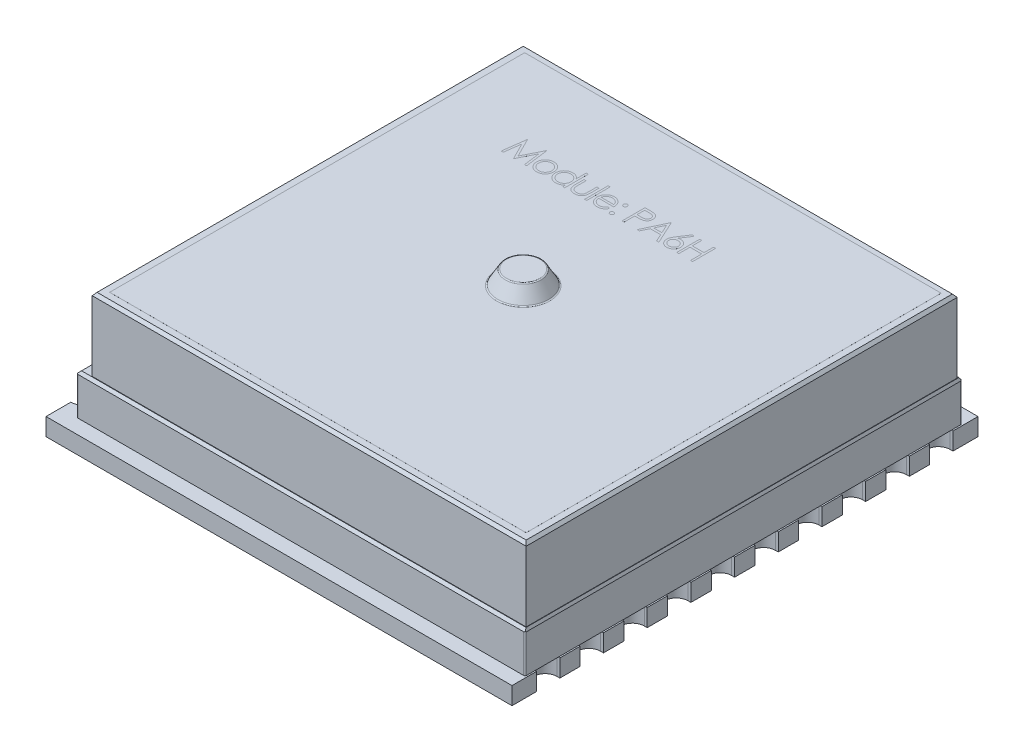
SolidWorks part; units mm, degrees
note: The reader was unsure of these and kept them because the rebuilt part matched: shared geometry of "Esboço11<8>", "Esboço11<9>", "Esboço11<11>", "Esboço11<12>", "Esboço11<15>", "Esboço11<16>", "Esboço11<17>", "Esboço11<19>", "Esboço11<20>".
ref_plane "Front Plane" through (0, 0, 0) normal (0, 0, 1) x (1, 0, 0)
ref_plane "Top Plane" through (0, 0, 0) normal (0, 1, 0) x (1, 0, 0)
ref_plane "Right Plane" through (0, 0, 0) normal (1, 0, 0) x (0, 0, -1)
sketch "Esboço1" plane through (0, 0, 0) normal (0, 1, 0) x (1, 0, 0)
  line L1 (0, 0) -> (16, 0)
  line L2 (0, 0) -> (0, -16)
  line L3 (0, -16) -> (16, -16)
  line L4 (16, 0) -> (16, -16)
  dimension "D1" = 16
  dimension "D2" = 16
extrude "BaseInicio" add sketch "Esboço1" along normal blind 0.6
sketch "Esboço2" plane through (0, 0.6, 0) normal (0, 1, 0) x (1, 0, 0)
  line L7 (0.55, -0.5) -> (15.95, -0.5)
  line L9 (15.95, -0.5) -> (15.95, -15.5)
  line L11 (15.95, -15.5) -> (0.55, -15.5)
  line L13 (0.55, -0.5) -> (0.55, -15.5)
extrude "BaseMeio" add sketch "Esboço2" along normal blind 1.4
sketch "Esboço5" plane through (0, 2, 0) normal (0, 1, 0) x (1, 0, 0)
  line L24 (1, -15.4145) -> (15.9, -15.4145)
  line L28 (1, -0.6145) -> (1, -15.4145)
  line L29 (1, -0.6145) -> (15.9, -0.6145)
  line L30 (15.9, -0.6145) -> (15.9, -15.4145)
extrude "BaseFim" add sketch "Esboço5" along normal blind 2.5
sketch "Esboço9" plane through (0, 4.5, 0) normal (0, 1, 0) x (1, 0, 0)
  circle A0 centre (8.2, -7.8145) radius 0.6
extrude "Chapeu" add sketch "Esboço9" along normal blind 0.5
draft "InclinaçãoChapeu" type of draft neutral plane draft angle 30 faces to draft 1 face at (8.2, 5, 8.4145) neutral plane through (8.2, 5, 7.8145) neutral plane normal (0, 1, 0) parameters "D1"=30
sketch "Esboço10" plane through (0, 0, 0) normal (0, -1, 0) x (1, 0, 0)
  line L1 (0, 0) -> (0, 16) construction
  line L4 (0, 0.75) -> (1, 0.75)
  line L7 (1, 1.75) -> (1, 0.75)
  line L8 (0, 0.75) -> (0, 1.75)
  line L9 (0, 1.75) -> (1, 1.75)
  line L11 (0, 2.25) -> (1, 2.25)
  line L12 (1, 3.25) -> (1, 2.25)
  line L13 (0, 2.25) -> (0, 3.25)
  line L14 (0, 3.25) -> (1, 3.25)
  line L16 (0, 3.75) -> (1, 3.75)
  line L17 (1, 4.75) -> (1, 3.75)
  line L18 (0, 3.75) -> (0, 4.75)
  line L19 (0, 4.75) -> (1, 4.75)
  line L21 (0, 5.25) -> (1, 5.25)
  line L22 (1, 6.25) -> (1, 5.25)
  line L23 (0, 5.25) -> (0, 6.25)
  line L24 (0, 6.25) -> (1, 6.25)
  line L26 (0, 6.75) -> (1, 6.75)
  line L27 (1, 7.75) -> (1, 6.75)
  line L28 (0, 6.75) -> (0, 7.75)
  line L29 (0, 7.75) -> (1, 7.75)
  line L31 (0, 8.25) -> (1, 8.25)
  line L32 (1, 9.25) -> (1, 8.25)
  line L33 (0, 8.25) -> (0, 9.25)
  line L34 (0, 9.25) -> (1, 9.25)
  line L36 (0, 9.75) -> (1, 9.75)
  line L37 (1, 10.75) -> (1, 9.75)
  line L38 (0, 9.75) -> (0, 10.75)
  line L39 (0, 10.75) -> (1, 10.75)
  line L41 (0, 11.25) -> (1, 11.25)
  line L42 (1, 12.25) -> (1, 11.25)
  line L43 (0, 11.25) -> (0, 12.25)
  line L44 (0, 12.25) -> (1, 12.25)
  line L46 (0, 12.75) -> (1, 12.75)
  line L47 (1, 13.75) -> (1, 12.75)
  line L48 (0, 12.75) -> (0, 13.75)
  line L49 (0, 13.75) -> (1, 13.75)
  line L51 (0, 14.25) -> (1, 14.25)
  line L52 (1, 15.25) -> (1, 14.25)
  line L53 (0, 14.25) -> (0, 15.25)
  line L54 (0, 15.25) -> (1, 15.25)
  line L86 (16, 16) -> (16, 0) construction
  line L87 (15, 0.7581) -> (16, 0.7581)
  line L88 (16, 1.7581) -> (16, 0.7581)
  line L89 (15, 0.7581) -> (15, 1.7581)
  line L90 (15, 1.7581) -> (16, 1.7581)
  line L92 (15, 2.2581) -> (16, 2.2581)
  line L93 (16, 3.2581) -> (16, 2.2581)
  line L94 (15, 2.2581) -> (15, 3.2581)
  line L95 (15, 3.2581) -> (16, 3.2581)
  line L97 (15, 3.7581) -> (16, 3.7581)
  line L98 (16, 4.7581) -> (16, 3.7581)
  line L99 (15, 3.7581) -> (15, 4.7581)
  line L100 (15, 4.7581) -> (16, 4.7581)
  line L102 (15, 5.2581) -> (16, 5.2581)
  line L103 (16, 6.2581) -> (16, 5.2581)
  line L104 (15, 5.2581) -> (15, 6.2581)
  line L105 (15, 6.2581) -> (16, 6.2581)
  line L107 (15, 6.7581) -> (16, 6.7581)
  line L108 (16, 7.7581) -> (16, 6.7581)
  line L109 (15, 6.7581) -> (15, 7.7581)
  line L110 (15, 7.7581) -> (16, 7.7581)
  line L112 (15, 8.2581) -> (16, 8.2581)
  line L113 (16, 9.2581) -> (16, 8.2581)
  line L114 (15, 8.2581) -> (15, 9.2581)
  line L115 (15, 9.2581) -> (16, 9.2581)
  line L117 (15, 9.7581) -> (16, 9.7581)
  line L118 (16, 10.7581) -> (16, 9.7581)
  line L119 (15, 9.7581) -> (15, 10.7581)
  line L120 (15, 10.7581) -> (16, 10.7581)
  line L122 (15, 11.2581) -> (16, 11.2581)
  line L123 (16, 12.2581) -> (16, 11.2581)
  line L124 (15, 11.2581) -> (15, 12.2581)
  line L125 (15, 12.2581) -> (16, 12.2581)
  line L127 (15, 12.7581) -> (16, 12.7581)
  line L128 (16, 13.7581) -> (16, 12.7581)
  line L129 (15, 12.7581) -> (15, 13.7581)
  line L130 (15, 13.7581) -> (16, 13.7581)
  line L132 (15, 14.2581) -> (16, 14.2581)
  line L133 (16, 15.2581) -> (16, 14.2581)
  line L134 (15, 14.2581) -> (15, 15.2581)
  line L135 (15, 15.2581) -> (16, 15.2581)
  point P56 (0, 0)
  point P61 (0, 0)
  point P66 (0, 0)
  point P71 (0, 0)
  point P76 (0, 0)
  point P81 (0, 0)
  point P86 (0, 0)
  point P91 (0, 0)
  point P97 (0, 0)
extrude "Pads" add sketch "Esboço10" along normal blind 0.0001
sketch "Esboço11" plane through (0, 0, 0) normal (-1, 0, 0) x (0, 0, 1)
  line L6 (0.5, 0.6) -> (15.5, 0.6) construction
  line L11 (0.85, -0.0001) -> (0.85, 0.6)
  line L20 (0, 0.6) -> (16, 0.6) construction
  line L22 (0.85, 0.6) -> (1.25, 0.6)
  line L23 (1.25, 0.6) -> (1.25, -0.0001)
  line L24 (1.25, -0.0001) -> (0.85, -0.0001)
  line L33 (2.35, -0.0001) -> (2.35, 0.6)
  line L35 (2.35, 0.6) -> (2.75, 0.6)
  line L36 (2.75, 0.6) -> (2.75, -0.0001)
  line L37 (2.75, -0.0001) -> (2.35, -0.0001)
  line L38 (3.85, -0.0001) -> (3.85, 0.6)
  line L39 (3.85, 0.6) -> (4.25, 0.6)
  line L40 (4.25, 0.6) -> (4.25, -0.0001)
  line L41 (4.25, -0.0001) -> (3.85, -0.0001)
  line L42 (5.35, -0.0001) -> (5.35, 0.6)
  line L43 (5.35, 0.6) -> (5.75, 0.6)
  line L44 (5.75, 0.6) -> (5.75, -0.0001)
  line L45 (5.75, -0.0001) -> (5.35, -0.0001)
  line L46 (6.85, -0.0001) -> (6.85, 0.6)
  line L47 (6.85, 0.6) -> (7.25, 0.6)
  line L48 (7.25, 0.6) -> (7.25, -0.0001)
  line L49 (7.25, -0.0001) -> (6.85, -0.0001)
  line L50 (8.35, -0.0001) -> (8.35, 0.6)
  line L51 (8.35, 0.6) -> (8.75, 0.6)
  line L52 (8.75, 0.6) -> (8.75, -0.0001)
  line L53 (8.75, -0.0001) -> (8.35, -0.0001)
  line L54 (9.85, -0.0001) -> (9.85, 0.6)
  line L55 (9.85, 0.6) -> (10.25, 0.6)
  line L56 (10.25, 0.6) -> (10.25, -0.0001)
  line L57 (10.25, -0.0001) -> (9.85, -0.0001)
  line L58 (11.35, -0.0001) -> (11.35, 0.6)
  line L59 (11.35, 0.6) -> (11.75, 0.6)
  line L60 (11.75, 0.6) -> (11.75, -0.0001)
  line L61 (11.75, -0.0001) -> (11.35, -0.0001)
  line L62 (12.85, -0.0001) -> (12.85, 0.6)
  line L63 (12.85, 0.6) -> (13.25, 0.6)
  line L64 (13.25, 0.6) -> (13.25, -0.0001)
  line L65 (13.25, -0.0001) -> (12.85, -0.0001)
  line L66 (14.35, -0.0001) -> (14.35, 0.6)
  line L67 (14.35, 0.6) -> (14.75, 0.6)
  line L68 (14.75, 0.6) -> (14.75, -0.0001)
  line L69 (14.75, -0.0001) -> (14.35, -0.0001)
  point P0 (0, 0)
revolve "Corte-Revolução1" cut sketch "Esboço11" angle 180 about L23
revolve "Corte-Revolução2" cut sketch "Esboço11<8>" angle 180 about L36
sketch "Esboço11<8>" plane through (0, 0, 0) normal (-1, 0, 0) x (0, 0, 1) same geometry as "Esboço11"
revolve "Corte-Revolução3" cut sketch "Esboço11<9>" angle 180 about L40
sketch "Esboço11<9>" plane through (0, 0, 0) normal (-1, 0, 0) x (0, 0, 1) same geometry as "Esboço11"
revolve "Corte-Revolução4" cut sketch "Esboço11<11>" angle 180 about L44
sketch "Esboço11<11>" plane through (0, 0, 0) normal (-1, 0, 0) x (0, 0, 1) same geometry as "Esboço11"
revolve "Corte-Revolução5" cut sketch "Esboço11<12>" angle 180 about L48
sketch "Esboço11<12>" plane through (0, 0, 0) normal (-1, 0, 0) x (0, 0, 1) same geometry as "Esboço11"
revolve "Corte-Revolução8" cut sketch "Esboço11<15>" angle 360 about L52
sketch "Esboço11<15>" plane through (0, 0, 0) normal (-1, 0, 0) x (0, 0, 1) same geometry as "Esboço11"
revolve "Corte-Revolução9" cut sketch "Esboço11<16>" angle 360 about L56
sketch "Esboço11<16>" plane through (0, 0, 0) normal (-1, 0, 0) x (0, 0, 1) same geometry as "Esboço11"
revolve "Corte-Revolução10" cut sketch "Esboço11<17>" angle 360 about L60
sketch "Esboço11<17>" plane through (0, 0, 0) normal (-1, 0, 0) x (0, 0, 1) same geometry as "Esboço11"
revolve "Corte-Revolução11" cut sketch "Esboço11<19>" angle 360 about L64
sketch "Esboço11<19>" plane through (0, 0, 0) normal (-1, 0, 0) x (0, 0, 1) same geometry as "Esboço11"
revolve "Corte-Revolução12" cut sketch "Esboço11<20>" angle 360 about L68
sketch "Esboço11<20>" plane through (0, 0, 0) normal (-1, 0, 0) x (0, 0, 1) same geometry as "Esboço11"
sketch "Esboço15" plane through (16, 0, 0) normal (1, 0, 0) x (0, 0, -1)
  line L0 (-13.6581, -0.0001) -> (-13.6581, 0.6)
  line L1 (-14.2581, -0.0001) -> (-15.2581, -0.0001) construction
  line L2 (-15.1581, -0.0001) -> (-15.1581, 0.6)
  line L3 (-16, 0.6) -> (0, 0.6) construction
  line L4 (-15.1581, 0.6) -> (-14.3581, 0.6)
  line L5 (-14.3581, 0.6) -> (-14.3581, -0.0001)
  line L6 (-14.3581, -0.0001) -> (-15.1581, -0.0001)
  line L9 (-13.6581, 0.6) -> (-12.8581, 0.6)
  line L10 (-12.8581, 0.6) -> (-12.8581, -0.0001)
  line L11 (-12.8581, -0.0001) -> (-13.6581, -0.0001)
  line L13 (-12.1581, -0.0001) -> (-12.1581, 0.6)
  line L14 (-12.1581, 0.6) -> (-11.3581, 0.6)
  line L15 (-11.3581, 0.6) -> (-11.3581, -0.0001)
  line L16 (-11.3581, -0.0001) -> (-12.1581, -0.0001)
  line L18 (-10.6581, -0.0001) -> (-10.6581, 0.6)
  line L19 (-10.6581, 0.6) -> (-9.8581, 0.6)
  line L20 (-9.8581, 0.6) -> (-9.8581, -0.0001)
  line L21 (-9.8581, -0.0001) -> (-10.6581, -0.0001)
  line L23 (-9.1581, -0.0001) -> (-9.1581, 0.6)
  line L24 (-9.1581, 0.6) -> (-8.3581, 0.6)
  line L25 (-8.3581, 0.6) -> (-8.3581, -0.0001)
  line L26 (-8.3581, -0.0001) -> (-9.1581, -0.0001)
  line L28 (-7.6581, -0.0001) -> (-7.6581, 0.6)
  line L29 (-7.6581, 0.6) -> (-6.8581, 0.6)
  line L30 (-6.8581, 0.6) -> (-6.8581, -0.0001)
  line L31 (-6.8581, -0.0001) -> (-7.6581, -0.0001)
  line L33 (-6.1581, -0.0001) -> (-6.1581, 0.6)
  line L34 (-6.1581, 0.6) -> (-5.3581, 0.6)
  line L35 (-5.3581, 0.6) -> (-5.3581, -0.0001)
  line L36 (-5.3581, -0.0001) -> (-6.1581, -0.0001)
  line L38 (-4.6581, -0.0001) -> (-4.6581, 0.6)
  line L39 (-4.6581, 0.6) -> (-3.8581, 0.6)
  line L40 (-3.8581, 0.6) -> (-3.8581, -0.0001)
  line L41 (-3.8581, -0.0001) -> (-4.6581, -0.0001)
  line L43 (-3.1581, -0.0001) -> (-3.1581, 0.6)
  line L44 (-3.1581, 0.6) -> (-2.3581, 0.6)
  line L45 (-2.3581, 0.6) -> (-2.3581, -0.0001)
  line L46 (-2.3581, -0.0001) -> (-3.1581, -0.0001)
  line L48 (-1.6581, -0.0001) -> (-1.6581, 0.6)
  line L49 (-1.6581, 0.6) -> (-0.8581, 0.6)
  line L50 (-0.8581, 0.6) -> (-0.8581, -0.0001)
  line L51 (-0.8581, -0.0001) -> (-1.6581, -0.0001)
extrude "Corte-extrusão3" cut sketch "Esboço15" against normal blind 0.5
fillet "Filete5" radius 0.4 4 edges at (15.5, 0.6, 14.7581) (15.5, -0.0001, 14.7581) (15.5, 0.2999, 15.1581) (15.5, 0.2999, 14.3581)
fillet "Filete6" radius 0.4 4 edges at (15.5, 0.6, 13.2581) (15.5, -0.0001, 13.2581) (15.5, 0.3, 13.6581) (15.5, 0.3, 12.8581)
fillet "Filete7" radius 0.4 4 edges at (15.5, 0.6, 11.7581) (15.5, -0.0001, 11.7581) (15.5, 0.3, 12.1581) (15.5, 0.3, 11.3581)
fillet "Filete8" radius 0.4 4 edges at (15.5, 0.6, 10.2581) (15.5, -0.0001, 10.2581) (15.5, 0.3, 10.6581) (15.5, 0.3, 9.8581)
fillet "Filete9" radius 0.4 4 edges at (15.5, 0.6, 8.7581) (15.5, -0.0001, 8.7581) (15.5, 0.3, 9.1581) (15.5, 0.3, 8.3581)
fillet "Filete10" radius 0.4 4 edges at (15.5, 0.6, 7.2581) (15.5, -0.0001, 7.2581) (15.5, 0.3, 7.6581) (15.5, 0.3, 6.8581)
fillet "Filete11" radius 0.4 4 edges at (15.5, 0.6, 5.7581) (15.5, -0.0001, 5.7581) (15.5, 0.3, 6.1581) (15.5, 0.3, 5.3581)
fillet "Filete12" radius 0.4 4 edges at (15.5, 0.6, 4.2581) (15.5, -0.0001, 4.2581) (15.5, 0.3, 4.6581) (15.5, 0.3, 3.8581)
fillet "Filete13" radius 0.4 4 edges at (15.5, 0.6, 2.7581) (15.5, -0.0001, 2.7581) (15.5, 0.3, 3.1581) (15.5, 0.3, 2.3581)
fillet "Filete14" radius 0.4 4 edges at (15.5, 0.6, 1.2581) (15.5, -0.0001, 1.2581) (15.5, 0.3, 1.6581) (15.5, 0.3, 0.8581)
chamfer "Chanfro2" distance 0.1 angle 45 1 edges at (0.55, 2, 8)
chamfer "Chanfro3" distance 0.1 angle 35 2 edges at (8.3, 2, 15.5) (8.3, 2, 0.5)
chamfer "Chanfro4" distance 0.1 angle 20 1 edges at (15.95, 2, 8)
chamfer "Chanfro5" distance 0.1 angle 40 4 edges at (15.9, 4.5, 8.0145) (8.45, 4.5, 15.4145) (1, 4.5, 8.0145) (8.45, 4.5, 0.6145)
sketch "Esboço16" plane through (0, 4.5, 0) normal (0, 1, 0) x (1, 0, 0)
  line L0 (1.3, -0.8662) -> (15.6, -0.8662)
  line L1 (1.3, -0.8662) -> (1.3, -15.1145)
  line L4 (15.6, -0.8662) -> (15.6, -15.1145)
  line L7 (15.6, -15.1145) -> (1.3, -15.1145)
extrude "Ressalto-extrusão7" add sketch "Esboço16" along normal blind 0.001
fillet "Filete15" radius 0.05 1 edges at (8.2, 5, 8.4145)
sketch "Esboço17" plane through (0, 4.501, 0) normal (0, 1, 0) x (1, 0, 0)
  text T0 "Module: PA6H" font "Century Gothic" height in points 3
extrude "Ressalto-extrusão8" add sketch "Esboço17" along normal blind 0.0001
fillet "Filete19" radius 0.05 1 edges at (8.2, 4.501, 6.9264)
fillet "Filete20" radius 0.05 4 edges at (0.55, 1.25, 0.5) (15.95, 1.25, 0.5) (15.95, 1.25, 15.5) (0.55, 1.25, 15.5)
